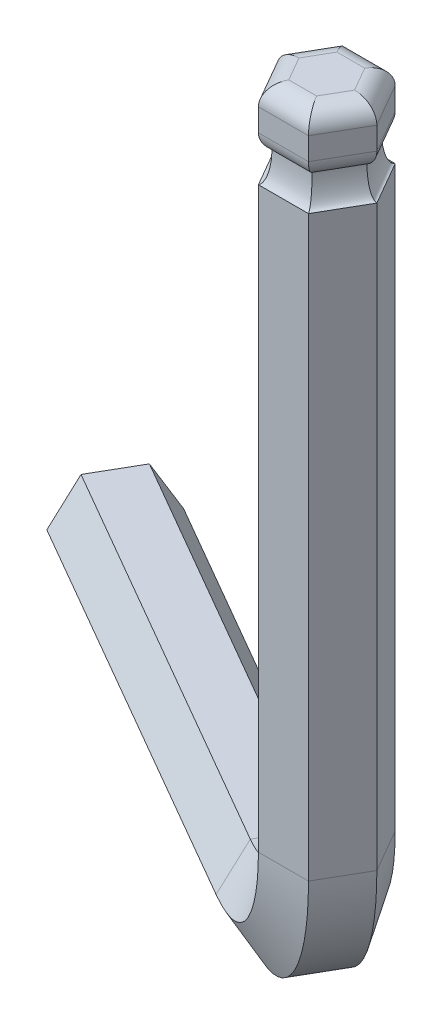
SolidWorks part; units mm, degrees
ref_plane "Front Plane" through (0, 0, 0) normal (0, 0, 1) x (1, 0, 0)
ref_plane "Top Plane" through (0, 0, 0) normal (0, 1, 0) x (1, 0, 0)
ref_plane "Right Plane" through (0, 0, 0) normal (1, 0, 0) x (0, 0, -1)
ref_plane "Plane1" through (0, 5, 0) normal (0, 1, 0) x (1, 0, 0)
sketch "Sketch2" plane through (0, 0, 0) normal (0, 1, 0) x (1, 0, 0)
  line L1 (8.6603, 0) -> (4.3301, 7.5)
  line L2 (4.3301, 7.5) -> (-4.3301, 7.5)
  line L3 (-4.3301, 7.5) -> (-8.6603, 0)
  line L4 (-8.6603, 0) -> (-4.3301, -7.5)
  line L5 (-4.3301, -7.5) -> (4.3301, -7.5)
  line L6 (4.3301, -7.5) -> (8.6603, 0)
  dimension "D1" = 15
sketch "Sketch3" plane through (0, 5, 0) normal (0, 1, 0) x (1, 0, 0)
  line L0 (-4.3301, -7.5) -> (4.3301, -7.5) construction
  line L1 (4.3301, -7.5) -> (8.6603, 0) construction
  line L2 (8.6603, 0) -> (4.3301, 7.5) construction
  line L3 (4.3301, 7.5) -> (-4.3301, 7.5) construction
  line L4 (-4.3301, 7.5) -> (-8.6603, 0) construction
  line L5 (-8.6603, 0) -> (-4.3301, -7.5) construction
  line L6 (-4.3301, -7.5) -> (4.3301, -7.5)
  line L7 (4.3301, -7.5) -> (8.6603, 0)
  line L8 (8.6603, 0) -> (4.3301, 7.5)
  line L9 (4.3301, 7.5) -> (-4.3301, 7.5)
  line L10 (-4.3301, 7.5) -> (-8.6603, 0)
  line L11 (-8.6603, 0) -> (-4.3301, -7.5)
  line L13 (6.9282, 0) -> (3.4641, 6)
  line L14 (3.4641, 6) -> (-3.4641, 6)
  line L15 (-3.4641, 6) -> (-6.9282, 0)
  line L16 (-6.9282, 0) -> (-3.4641, -6)
  line L17 (-3.4641, -6) -> (3.4641, -6)
  line L18 (3.4641, -6) -> (6.9282, 0)
  circle A0 centre (0, 0) radius 6 construction
  dimension "D1" = 12
extrude "Boss-Extrude1" add sketch "Sketch3" against normal blind 5 contours L15 L16 L17 L18 L13 L14
extrude "Boss-Extrude2" add sketch "Sketch3<4>" along normal blind 10 contours L11 L6 L7 L8 L9 L10
sketch "Sketch3<4>" plane through (0, 5, 0) normal (0, 1, 0) x (1, 0, 0) same geometry as "Sketch3"
extrude "Boss-Extrude3" add sketch "Sketch2" against normal blind 100 contours L6 L1 L2 L3 L4 L5
sketch "Sketch11" plane through (0, -100, 0) normal (0, -1, 0) x (1, 0, 0)
  line L0 (0, 0) -> (-17.3205, -10)
  line L1 (-17.3205, -10) -> (-24.9968, 3.2958)
  line L6 (4.3301, 7.5) -> (-4.3301, 7.5)
  line L7 (-4.3301, 7.5) -> (-8.6603, 0)
  line L8 (-8.6603, 0) -> (-4.3301, -7.5)
  line L9 (-4.3301, -7.5) -> (4.3301, -7.5)
  line L10 (4.3301, -7.5) -> (8.6603, 0)
  line L11 (8.6603, 0) -> (4.3301, 7.5)
  line L12 (4.3301, 7.5) -> (-4.3301, 7.5)
  line L13 (-4.3301, 7.5) -> (-8.6603, 0)
  line L14 (-8.6603, 0) -> (-4.3301, -7.5)
  line L15 (-4.3301, -7.5) -> (4.3301, -7.5)
  line L16 (4.3301, -7.5) -> (8.6603, 0)
  line L17 (8.6603, 0) -> (4.3301, 7.5)
  dimension "D2" = 20
revolve "Revolve1" add sketch "Sketch11" angle 90 about L1 reverse direction yes
sketch "Sketch12" plane through (-6.4952, 0, -3.75) normal (-0.866, 0, -0.5) x (-0.5, 0, 0.866)
  line L0 (-4.3301, -100) -> (4.3301, -100)
  line L5 (-4.3301, -100) -> (4.3301, -100)
  line L6 (-4.3301, -100) -> (4.3301, -100)
  line L8 (4.3301, 0) -> (-4.3301, 0)
  line L9 (-4.3301, 0) -> (-4.3301, -100)
  line L15 (4.3301, -100) -> (4.3301, 0)
  line L16 (4.3301, 0) -> (-4.3301, 0)
  line L17 (-4.3301, 0) -> (-4.3301, -100)
  line L23 (4.3301, -100) -> (4.3301, 0)
  dimension "D1" = 0
fillet "Fillet1" radius 1.5 6 edges at (5.1962, 0, -3) (5.1962, 0, 3) (0, 0, 6) (-5.1962, 0, 3) (-5.1962, 0, -3) (0, 0, -6) second distance 5 first distance on face at (0, 0, 0)
fillet "Fillet3" radius 3.3333 12 edges at (-6.4952, 5, -3.75) (0, 5, -7.5) (6.4952, 5, -3.75) (6.4952, 5, 3.75) (0, 5, 7.5) (-6.4952, 5, 3.75) (-6.4952, 15, 3.75) (-6.4952, 15, -3.75) (0, 15, -7.5) (6.4952, 15, 3.75) (6.4952, 15, -3.75) (0, 15, 7.5)
sketch "Sketch13" plane through (-17.3205, 0, -10) normal (-0.866, 0, -0.5) x (-0.5, 0, 0.866)
  line L6 (4.3301, -127.5) -> (8.6603, -120)
  line L7 (8.6603, -120) -> (4.3301, -112.5)
  line L8 (4.3301, -112.5) -> (-4.3301, -112.5)
  line L9 (-4.3301, -112.5) -> (-8.6603, -120)
  line L10 (-8.6603, -120) -> (-4.3301, -127.5)
  line L11 (-4.3301, -127.5) -> (4.3301, -127.5)
  line L12 (4.3301, -127.5) -> (8.6603, -120)
  line L13 (8.6603, -120) -> (4.3301, -112.5)
  line L14 (4.3301, -112.5) -> (-4.3301, -112.5)
  line L15 (-4.3301, -112.5) -> (-8.6603, -120)
  line L16 (-8.6603, -120) -> (-4.3301, -127.5)
  line L17 (-4.3301, -127.5) -> (4.3301, -127.5)
  dimension "D1" = 0
extrude "Boss-Extrude5" add sketch "Sketch13" along normal blind 80
equation "\"outerD\"= 15"
equation "\"D1@Sketch2\"=\"outerD\""
equation "\"innerD\"= 12"
equation "\"D1@Sketch3\"=\"innerD\""
equation "\"toBall\"=5"
equation "\"D1@Plane1\"=\"toBall\""
equation "\"D1@Boss-Extrude1\"=\"toBall\""
equation "\"ball\"=10"
equation "\"D1@Boss-Extrude2\"=\"ball\""
equation "\"len\"=5"
equation "\"D1@Boss-Extrude3\"=\"len\""
equation "\"len2\"=100"
equation "\"D1@Fillet1\"=(\"outerD\"-\"innerD\")/2"
equation "\"D2@Fillet1\"=\"toBall\""
equation "\"D1@Fillet3\"=\"ball\"/3"
equation "\"bendRad\"=20"
equation "\"D2@Sketch11\"=\"bendRad\""
equation "\"D1@Boss-Extrude5\"=\"len2\"-\"bendRad\""
